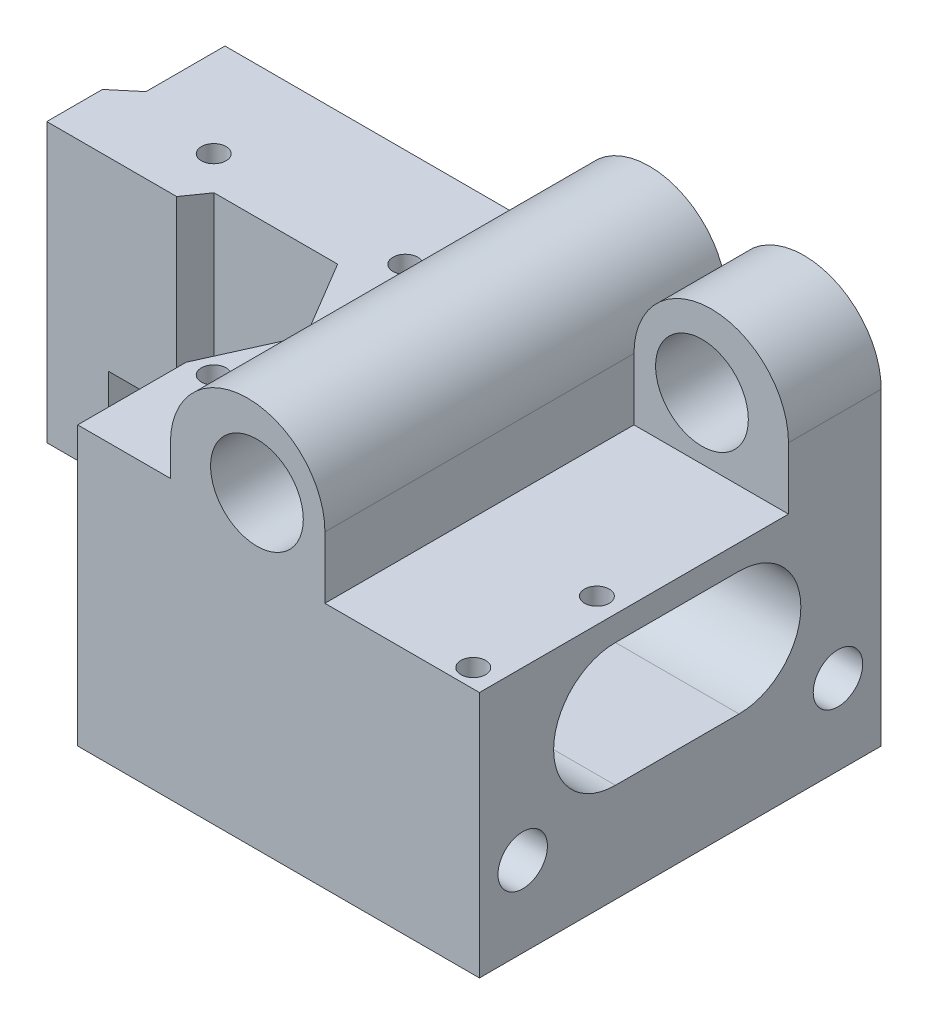
SolidWorks part; units mm, degrees
material "ABS"
ref_plane "Front Plane" through (0, 0, 0) normal (0, 0, 1) x (1, 0, 0)
ref_plane "Top Plane" through (0, 0, 0) normal (0, 1, 0) x (1, 0, 0)
ref_plane "Right Plane" through (0, 0, 0) normal (1, 0, 0) x (0, 0, -1)
sketch "Sketch1" plane through (0, 0, 0) normal (0, 0, 1) x (1, 0, 0)
  line L0 (0, 0) -> (50, 0)
  line L1 (50, 0) -> (50, 50)
  line L2 (0, 50) -> (0, 0)
  arc A0 (50, 50) -> (25, 58.6603) centre (36, 50) ccw
  arc A1 (25, 58.6603) -> (0, 50) centre (14, 50) ccw
  circle A2 centre (36, 50) radius 7.5
  circle A3 centre (14, 50) radius 7.5
  dimension "D2" = 22
  dimension "D5" = 15
  dimension "D1" = 50
  dimension "D4" = 50
extrude "Boss-Extrude1" add sketch "Sketch1" along normal blind 15
sketch "Sketch2" plane through (0, 0, 15) normal (0, 0, 1) x (1, 0, 0)
  line L0 (0, 0) -> (0, 50)
  line L4 (25, 50) -> (25, 0)
  line L6 (38, 0) -> (50, 0)
  line L7 (50, 0) -> (50, 50)
  line L8 (0, 0) -> (50, 0)
  circle A1 centre (14, 50) radius 7.5
  circle A2 centre (36, 50) radius 7.5 construction
  circle A3 centre (14, 50) radius 7.5 construction
  arc A4 (0, 50) -> (25, 50) centre (12.5, 50) cw
  arc A5 (50, 50) -> (25, 50) centre (37.5, 50) ccw
  circle M5 centre (14, 50) radius 7.5
  line M6 (0, 50) -> (0, 0)
  line M7 (0, 0) -> (50, 0)
  arc M9 (50, 50) -> (25, 58.6603) centre (36, 50) ccw
  arc M10 (25, 58.6603) -> (0, 50) centre (14, 50) ccw
extrude "Boss-Extrude2" add sketch "Sketch2" along normal blind 50 contours A4 L4 M6 M7 M5 region at (12.299, 27.2902, 15)
sketch "Sketch3" plane through (0, 0, 0) normal (0, 0, -1) x (-1, 0, 0)
  line L0 (0, 50) -> (0, 0) construction
  line L1 (-50, 0) -> (0, 0)
  line L2 (-50, 0) -> (-50, 40)
  line L3 (-50, 40) -> (0, 40)
  line L4 (0, 0) -> (0, 40)
  dimension "D1" = 40
extrude "Boss-Extrude3" add sketch "Sketch3" against normal blind 65
sketch "Sketch4" plane through (0, 0, 0) normal (-1, 0, 0) x (0, 0, 1)
  line L0 (23, 26) -> (43, 26) construction
  line L1 (23, 36) -> (43, 36)
  line L2 (23, 16) -> (43, 16)
  line L4 (65, 0) -> (0, 0) construction
  line L5 (65, 50) -> (65, 0) construction
  arc A0 (23, 36) -> (23, 16) centre (23, 26) ccw
  arc A1 (43, 16) -> (43, 36) centre (43, 26) ccw
  point P2 (33, 26)
  dimension "D2" = 10
  dimension "D4" = 22
  dimension "D1" = 20
  dimension "D3" = 16
extrude "Cut-Extrude1" cut sketch "Sketch4" against normal through all
sketch "Sketch6" plane through (0, 0, 0) normal (0, -1, 0) x (1, 0, 0)
  line L0 (0, 65) -> (-15, 65)
  line L1 (-15, 65) -> (-15, 47.4506)
  line L2 (-15, 47.4506) -> (-8.9799, 34.0615)
  line L3 (-8.9799, 34.0615) -> (-16.4946, 21.4506)
  line L4 (-16.4946, 21.4506) -> (-36.4946, 21.4506)
  line L5 (-36.4946, 21.4506) -> (-38.9799, 25)
  line L6 (-38.9799, 25) -> (-60, 25)
  line L7 (-60, 25) -> (-60, 16)
  line L8 (-60, 16) -> (-56.1698, 12.7861)
  line L9 (-56.1698, 12.7861) -> (-56.1698, 0)
  line L10 (-56.1698, 0) -> (0, 0)
  line L13 (0, 0) -> (25, 0) construction
  line L15 (0, 65) -> (0, 0)
  line L16 (0, 65) -> (50, 65) construction
  line L17 (0, 65) -> (0, 0) construction
  circle A0 centre (-41.9946, 16) radius 2
  circle A1 centre (-10.9946, 16) radius 2
  circle A2 centre (-10.9946, 47) radius 2
  dimension "D1" = 4
  dimension "D3" = 31
  dimension "D4" = 8.9799
  dimension "D11" = 16
  dimension "D2" = 31
  dimension "D5" = 56.1698
  dimension "D6" = 15
  dimension "D7" = 26
  dimension "D8" = 125
  dimension "D9" = 125
  dimension "D10" = 5
  dimension "D12" = 25
  dimension "D13" = 20
  dimension "D14" = 5.5
  dimension "D15" = 30
  dimension "D16" = 130
  dimension "D17" = 9
extrude "Cut-Extrude2" cut sketch "Sketch2<3>" against normal through all contours A5 A4 M9 M10 region at (9.5874, 62.7381, 15)
sketch "Sketch2<3>" plane through (0, 0, 15) normal (0, 0, 1) x (1, 0, 0) same geometry as "Sketch2"
extrude "Boss-Extrude7" add sketch "Sketch6" against normal blind 30 from offset 15 offset against normal yes
sketch "Sketch8" plane through (0, 15, 0) normal (0, -1, 0) x (-1, 0, 0)
  line L0 (60, -25) -> (50, -25)
  line L1 (38.9799, -25) -> (60, -25) construction
  line L2 (50, -25) -> (50, -10)
  line L3 (50, -10) -> (0, -10)
  line L4 (0, -10) -> (0, 0)
  line L5 (0, 0) -> (56.1698, 0)
  line L6 (56.1698, 0) -> (56.1698, -12.7861)
  line L7 (56.1698, -12.7861) -> (60, -16)
  line L8 (60, -16) -> (60, -25)
  line L9 (15, -65) -> (0, -65)
  line L10 (0, -65) -> (15, -65) construction
  line L11 (0, -65) -> (-50, -65)
  line L12 (-50, -65) -> (-50, 0)
  line L13 (-50, 0) -> (0, 0)
  line L17 (0, -10) -> (0, -65)
  line L18 (0, -55) -> (15, -55)
  line L19 (15, -55) -> (15, -65)
  line L20 (0, 0) -> (-25, 0) construction
  line L21 (-50, -65) -> (-50, -15) construction
  line L22 (0, 0) -> (0, -65) construction
  line M38 (15, -65) -> (15, -47.4506)
  line M49 (0, -65) -> (15, -65)
  dimension "D1" = 10
  dimension "D2" = 10
  dimension "D3" = 10
extrude "Boss-Extrude10" add sketch "Sketch8" along normal blind 15 contours L18 L17 M49 M38 | L8 L0 L2 L3 L4 L5 L6 L7 region at (-7.5, 15, 60)
sketch "Sketch9" plane through (0, 0, 0) normal (-1, 0, 0) x (0, 0, 1)
  line L0 (0, 50) -> (0, 45) construction
  line L1 (65, 50) -> (65, 45) construction
  circle A0 centre (58, 13) radius 4
  circle A1 centre (7, 13) radius 4
  arc A2 (23, 36) -> (23, 16) centre (23, 26) ccw construction
  dimension "D1" = 8
  dimension "D2" = 13
  dimension "D3" = 7
  dimension "D4" = 7
extrude "Cut-Extrude3" cut sketch "Sketch9" against normal through all
sketch "Sketch10" plane through (0, 0, 0) normal (1, 0, 0) x (0, 0, -1)
  line L0 (-37, 26) -> (-27, 26) construction
  line L1 (-37, 33) -> (-27, 33)
  line L2 (-37, 19) -> (-27, 19)
  line L3 (-23, 16) -> (-43, 16) construction
  arc A0 (-37, 33) -> (-37, 19) centre (-37, 26) ccw
  arc A1 (-27, 19) -> (-27, 33) centre (-27, 26) ccw
  point P4 (-32, 26)
  dimension "D1" = 10
  dimension "D3" = 7
  dimension "D2" = 9
  dimension "D4" = 10
extrude "Cut-Extrude6" cut sketch "Sketch10" against normal blind 20
sketch "Esquisse1" plane through (0, 40, 0) normal (0, 1, 0) x (1, 0, 0)
  line L0 (50, -65) -> (50, -15) construction
  line L1 (25, -65) -> (50, -65) construction
  circle A0 centre (46, -42) radius 2
  circle A1 centre (46, -62) radius 2
  dimension "D1" = 4
  dimension "D2" = 4
  dimension "D3" = 20
  dimension "D4" = 3
  dimension "D5" = 4
extrude "Enlèv. mat.-Extru.1" cut sketch "Esquisse1" against normal blind 10
